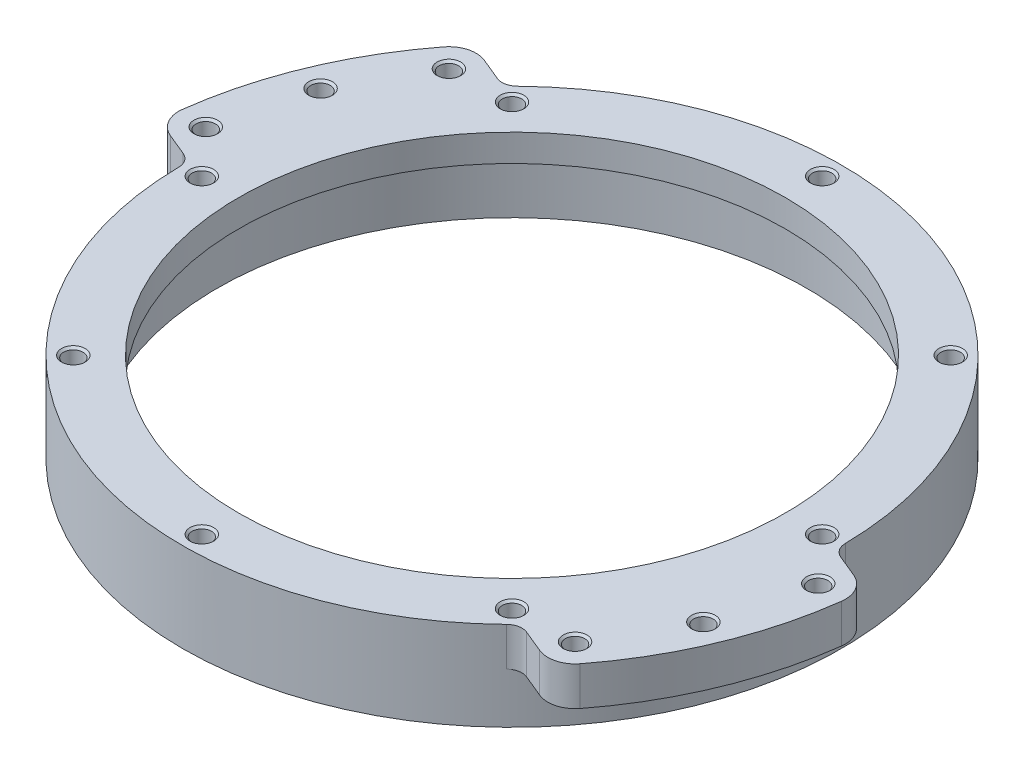
SolidWorks part; units mm, degrees
note: '?' marks a value the reader was unsure of.
material "6061-T6 (SS)"
ref_plane "前视基准面" through (0, 0, 0) normal (0, 0, 1) x (1, 0, 0)
ref_plane "上视基准面" through (0, 0, 0) normal (0, 1, 0) x (1, 0, 0)
ref_plane "右视基准面" through (0, 0, 0) normal (1, 0, 0) x (0, 0, -1)
sketch "草图1" plane through (0, 0, 0) normal (0, 1, 0) x (1, 0, 0)
  circle A3 centre (0, 0) radius 38
  circle A4 centre (0, 0) radius 42.5
  dimension "D3" = 76
  dimension "D1" = 4.5
extrude "凸台-拉伸1" add sketch "草图1" along normal blind 11.5
sketch "草图2" plane through (0, 11.5, 0) normal (0, 1, 0) x (1, 0, 0)
  circle A0 centre (0, 0) radius 38
  circle A1 centre (0, 0) radius 35.25
  circle A2 centre (0, 0) radius 38 construction
  dimension "D1" = 70.5
extrude "凸台-拉伸2" add sketch "草图2" against normal blind 3.5
sketch "草图3" plane through (0, 0, 0) normal (0, -1, 0) x (1, 0, 0)
  line L0 (0, 0) -> (0, -40) construction
  circle A16 centre (0, -40) radius 1
  circle A17 centre (-28.2843, -28.2843) radius 1
  circle A18 centre (-40, 0) radius 1
  circle A19 centre (-28.2843, 28.2843) radius 1
  circle A20 centre (0, 40) radius 1
  circle A21 centre (28.2843, 28.2843) radius 1
  circle A22 centre (40, 0) radius 1
  circle A23 centre (28.2843, -28.2843) radius 1
  point P19 (0, 0)
  dimension "D1" = 2
  dimension "D3" = 80
  dimension "D2" = 8
extrude "切除-拉伸1" cut sketch "草图3" against normal through all
sketch "草图5" plane through (0, 11.5, 0) normal (0, 1, 0) x (1, 0, 0)
  line L0 (32.5668, -13.4896) -> (53.3102, -22.0818) construction
  line L1 (0, 0) -> (-6.4471, -15.5646) construction
  line L2 (34.7191, -31.1582) -> (30.6288, -29.464)
  line L3 (46.5823, -2.5179) -> (42.492, -0.8237)
  line L4 (-34.7191, 31.1582) -> (-30.6288, 29.464)
  line L5 (-46.5823, 2.5179) -> (-42.492, 0.8237)
  line L6 (0, 0) -> (19.9054, 0) construction
  circle A0 centre (0, 0) radius 35.25 construction
  circle A1 centre (36.0585, -27.9246) radius 1.15
  circle A2 centre (45.2429, -5.7515) radius 1.15
  circle A3 centre (-36.0585, 27.9246) radius 1.15
  circle A4 centre (-45.2429, 5.7515) radius 1.15
  arc A5 (34.7191, -31.1582) -> (38.8257, -30.0676) centre (36.0585, -27.9246) ccw
  arc A6 (48.715, -6.1929) -> (46.5823, -2.5179) centre (45.2429, -5.7515) ccw
  arc A7 (36.0585, -27.9246) -> (45.2429, -5.7515) centre (0, 0) ccw construction
  circle A8 centre (0, 0) radius 42.5 construction
  arc A9 (38.8257, -30.0676) -> (48.715, -6.1929) centre (0, 0) ccw
  arc A10 (30.6288, -29.464) -> (42.492, -0.8237) centre (0, 0) ccw
  arc A11 (-38.8257, 30.0676) -> (-34.7191, 31.1582) centre (-36.0585, 27.9246) cw
  arc A12 (-48.715, 6.1929) -> (-38.8257, 30.0676) centre (0, 0) cw
  arc A13 (-42.492, 0.8237) -> (-30.6288, 29.464) centre (0, 0) cw
  arc A14 (-46.5823, 2.5179) -> (-48.715, 6.1929) centre (-45.2429, 5.7515) cw
  circle A16 centre (-42.1354, 17.453) radius 1.15
  circle A17 centre (42.1354, -17.453) radius 1.15
  circle A18 centre (45.2429, -5.7515) radius 2.75 construction
  dimension "D2" = 2.3
  dimension "D4" = 7
  dimension "D6" = 5.5
  dimension "D3" = 88
  dimension "D1" = 24
  dimension "D5" = 22.5
extrude "凸台-拉伸3" add sketch "草图5" against normal blind 5
fillet "圆角1" radius 2 4 edges at (-42.492, 9, -0.8237) (-30.6288, 9, -29.464) (42.492, 9, 0.8237) (30.6288, 9, 29.464)
hole_wizard "M3 螺纹孔1" positions "3D草图1" profile "草图6" tap size "M3" standard "ISO" end condition through all
sketch3d "3D草图1"
  line L1 (40, 11.5, 0) -> (40, 0, 0) construction
  line L2 (28.2843, 11.5, -28.2843) -> (28.2843, 0, -28.2843) construction
  line L3 (0, 11.5, -40) -> (0, 0, -40) construction
  line L4 (-28.2843, 11.5, -28.2843) -> (-28.2843, 0, -28.2843) construction
  line L5 (-40, 11.5, 0) -> (-40, 0, 0) construction
  line L6 (-28.2843, 11.5, 28.2843) -> (-28.2843, 0, 28.2843) construction
  line L9 (42.1354, 6.5, 17.453) -> (42.1354, 11.5, 17.453) construction
  line L10 (45.2429, 6.5, 5.7515) -> (45.2429, 11.5, 5.7515) construction
  line L11 (-45.2429, 6.5, -5.7515) -> (-45.2429, 11.5, -5.7515) construction
  line L12 (-45.2429, 6.5, -5.7515) -> (-45.2429, 11.5, -5.7515) construction
  line L13 (-42.1354, 6.5, -17.453) -> (-42.1354, 11.5, -17.453) construction
  line L14 (-36.0585, 6.5, -27.9246) -> (-36.0585, 11.5, -27.9246) construction
  point P4 (40, 11.5, 0)
  point P8 (28.2843, 11.5, -28.2843)
  point P12 (0, 11.5, -40)
  point P16 (-28.2843, 11.5, -28.2843)
  point P20 (-40, 11.5, 0)
  point P24 (-28.2843, 11.5, 28.2843)
  point P36 (42.1354, 11.5, 17.453)
  point P40 (45.2429, 11.5, 5.7515)
  point P44 (-45.2429, 11.5, -5.7515)
  point P50 (-42.1354, 11.5, -17.453)
  point P54 (-36.0585, 11.5, -27.9246)
sketch "草图6" plane through (40, 11.5, 0) normal (1, 0, 0) x (0, 0, 1)
  line L0 (0, 0) -> (0, 11.5)
  line L1 (0, 11.5) -> (1.25, 11.5)
  line L2 (1.25, 11.5) -> (1.25, 0.275)
  line L3 (1.25, 0.275) -> (1.525, 0)
  line L5 (1.525, 0) -> (0, 0)
  line L6 (-1.25, 0.275) -> (-1.525, 0) construction
  line L11 (0, -6.35) -> (0, 107.95) construction
  dimension "通孔螺纹孔钻头直径" = 2.5
  dimension "通孔螺纹孔钻头深度" = 11.5
  dimension "近端锥形沉头孔直径" = 3.05
  dimension "近端锥形沉头孔角度" = 90
cosmetic thread "孔螺蚊线2" parameters "D2"=3
cosmetic thread "孔螺蚊线3" parameters "D2"=3
cosmetic thread "孔螺蚊线4" parameters "D2"=3
cosmetic thread "孔螺蚊线5" parameters "D2"=3
cosmetic thread "孔螺蚊线6" parameters "D2"=3
cosmetic thread "孔螺蚊线7" parameters "D2"=3
cosmetic thread "孔螺蚊线15" parameters "D2"=3
cosmetic thread "孔螺蚊线16" parameters "D2"=3
cosmetic thread "孔螺蚊线17" parameters "D2"=3
cosmetic thread "孔螺蚊线18" parameters "D2"=3
cosmetic thread "孔螺蚊线19" parameters "D2"=3
ref_axis "基准轴1" through (42.1354, 6.5, 17.453) along (0, 1, 0)?
ref_axis "基准轴2" through (-42.1354, 6.5, -17.453) along (0, 1, 0)?
ref_plane "基准面1" through (0, 0, 0) normal (-0.3827, 0, 0.9239) x (0.9239, 0, 0.3827)
sketch "草图7" plane through (0, 11.5, 0) normal (0, 1, 0) x (1, 0, 0)
  line L0 (42.1354, -17.453) -> (0, 0) construction
ref_plane "基准面2" through (0, 0, 0) normal (0.3827, 0, -0.9239) x (-0.9239, 0, -0.3827)
hole_wizard "M3 螺纹孔2" positions "3D草图2" profile "草图8" tap size "M3" standard "ISO" end condition through all
sketch3d "3D草图2"
  line L0 (36.0585, 6.5, 27.9246) -> (36.0585, 11.5, 27.9246) construction
  line L1 (28.2843, 11.5, 28.2843) -> (28.2843, 0, 28.2843) construction
  line L2 (0, 11.5, 40) -> (0, 0, 40) construction
  point P0 (36.0585, 11.5, 27.9246)
  point P4 (28.2843, 11.5, 28.2843)
  point P8 (0, 11.5, 40)
sketch "草图8" plane through (36.0585, 11.5, 27.9246) normal (1, 0, 0) x (0, 0, 1)
  line L0 (0, 0) -> (0, 11.5)
  line L1 (0, 11.5) -> (1.25, 11.5)
  line L2 (1.25, 11.5) -> (1.25, 0.275)
  line L3 (1.25, 0.275) -> (1.525, 0)
  line L5 (1.525, 0) -> (0, 0)
  line L6 (-1.25, 0.275) -> (-1.525, 0) construction
  line L11 (0, -6.35) -> (0, 107.95) construction
  dimension "通孔螺纹孔钻头直径" = 2.5
  dimension "通孔螺纹孔钻头深度" = 11.5
  dimension "近端锥形沉头孔直径" = 3.05
  dimension "近端锥形沉头孔角度" = 90
cosmetic thread "孔螺蚊线20" parameters "D2"=3
cosmetic thread "孔螺蚊线21" parameters "D2"=3
cosmetic thread "孔螺蚊线22" parameters "D2"=3
